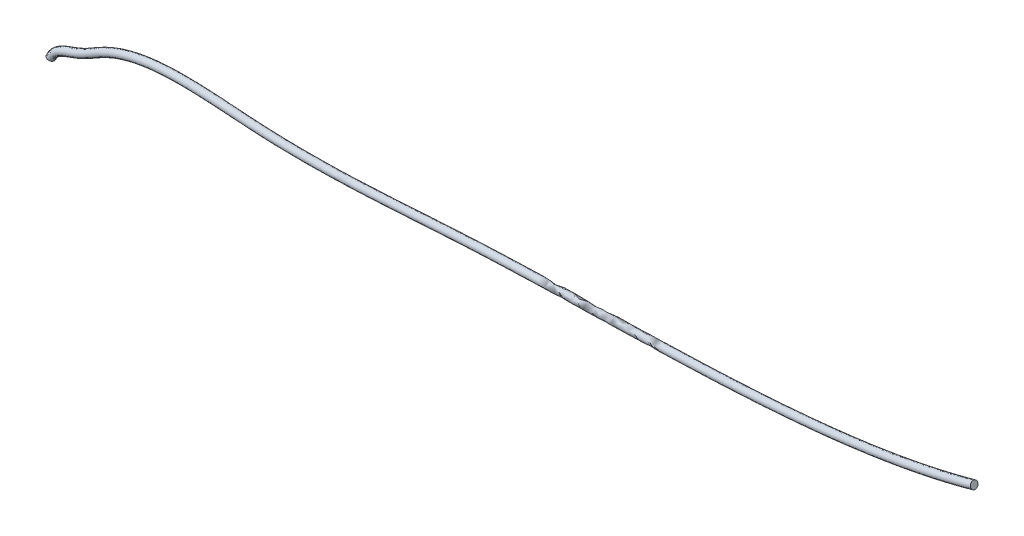
SolidWorks part; units mm, degrees
ref_plane "前视基准面" through (0, 0, 0) normal (0, 0, 1) x (1, 0, 0)
ref_plane "上视基准面" through (0, 0, 0) normal (0, 1, 0) x (1, 0, 0)
ref_plane "右视基准面" through (0, 0, 0) normal (1, 0, 0) x (0, 0, -1)
sketch "草图1" plane through (0, 0, 0) normal (0, 0, 1) x (1, 0, 0)
  spline S0 degree 3 poles (35.3865, -3.5328) (24.846, -6.4545) (7.4616, -5.5855) (-11.5671, -7.4684) (-21.3336, -5.9867) (-25.3397, -8.7072) (-26.9534, -9.0147) (-27.2225, -9.7216) knots 0 0 0 0 0.542722 0.766928 0.935398 0.96468 1 1 1 1
sweep "扫描1" add path "草图1" circular profile diameter 0.5 parameters "D3"=0.5
